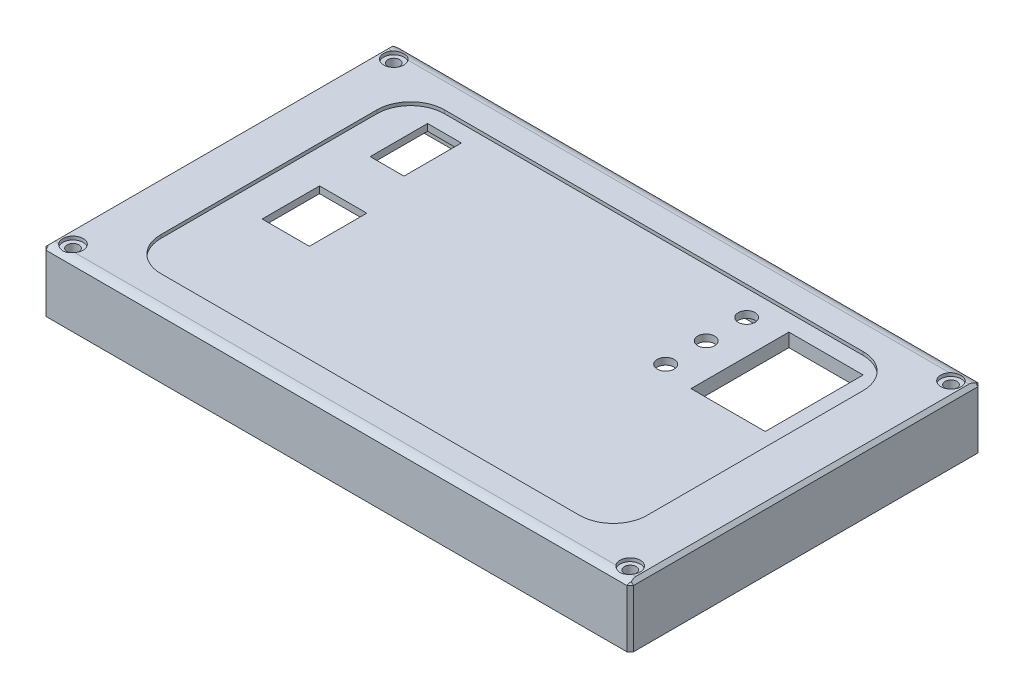
SolidWorks part; units mm, degrees
ref_plane "Front Plane" through (0, 0, 0) normal (0, 0, 1) x (1, 0, 0)
ref_plane "Top Plane" through (0, 0, 0) normal (0, 1, 0) x (1, 0, 0)
ref_plane "Right Plane" through (0, 0, 0) normal (1, 0, 0) x (0, 0, -1)
sketch "Sketch1" plane through (0, 0, 0) normal (0, 1, 0) x (1, 0, 0)
  line L1 (0, 0) -> (174, 0)
  line L2 (0, 0) -> (0, 104)
  line L3 (0, 104) -> (174, 104)
  line L4 (174, 0) -> (174, 104)
  dimension "D1" = 104
  dimension "D2" = 174
extrude "Boss-Extrude3" add sketch "Sketch1" against normal blind 18
sketch "Sketch5" plane through (0, -18, 0) normal (0, -1, 0) x (-1, 0, 0)
  line L0 (-174, 0) -> (-174, 104) construction
  line L1 (-173, 103) -> (-1, 103)
  line L2 (-173, 103) -> (-173, 1)
  line L3 (-173, 1) -> (-1, 1)
  line L4 (-1, 103) -> (-1, 1)
  line L5 (0, 0) -> (-174, 0) construction
  dimension "D1" = 172
  dimension "100mm" = 102
  dimension "D2" = 1
  dimension "D3" = 1
extrude "Cut-Extrude2" cut sketch "Sketch5" against normal blind 10
sketch "Sketch6" plane through (0, -8, 0) normal (0, -1, 0) x (1, 0, 0)
  line L0 (1, -103) -> (173, -103) construction
  line L1 (172, -102) -> (2, -102)
  line L2 (172, -102) -> (172, -2)
  line L3 (172, -2) -> (2, -2)
  line L4 (2, -102) -> (2, -2)
  line L5 (173, -103) -> (173, -1) construction
  dimension "D1" = 100
  dimension "D2" = 170
  dimension "D3" = 1
  dimension "D4" = 1
extrude "Cut-Extrude4" cut sketch "Sketch6" against normal blind 5
sketch "Sketch7" plane through (0, -3, 0) normal (0, -1, 0) x (-1, 0, 0)
  line L0 (-2, 102) -> (-172, 102) construction
  line L1 (-172, 102) -> (-172, 2) construction
  line L2 (-2, 2) -> (-2, 102) construction
  line L3 (-172, 2) -> (-2, 2) construction
  line L4 (-172, 102) -> (-172, 95.1699)
  line L5 (-172, 102) -> (-165.1699, 102)
  line L6 (-2, 102) -> (-2, 95.1699)
  line L7 (-2, 102) -> (-8.8301, 102)
  line L8 (-2, 2) -> (-2, 8.8301)
  line L9 (-2, 2) -> (-8.8301, 2)
  line L10 (-172, 2) -> (-172, 8.8301)
  line L11 (-172, 2) -> (-165.1699, 2)
  circle A0 centre (-4.5, 99.5) radius 5
  circle A1 centre (-169.5, 99.5) radius 5
  circle A2 centre (-169.5, 4.5) radius 5
  circle A3 centre (-4.5, 4.5) radius 5
  line M5 (-172, 102) -> (-172, 2)
  line M6 (-172, 2) -> (-2, 2)
  line M7 (-2, 2) -> (-2, 102)
  line M8 (-2, 102) -> (-172, 102)
  dimension "D1" = 2.5
  dimension "D2" = 2.5
  dimension "D3" = 2.5
  dimension "D4" = 2.5
  dimension "D5" = 2.5
  dimension "D6" = 2.5
  dimension "D7" = 2.5
  dimension "D8" = 2.5
extrude "Boss-Extrude4" add sketch "Sketch7" along normal blind 5 contours A2 M6 M5 | A0 M8 M7 | A3 M7 M6 | A1 M5 M8 region at (168.5382, -3, -98.5382) region at (168.5382, -3, -5.4618) region at (5.4618, -3, -98.5382) region at (5.4618, -3, -5.4618)
sketch "Sketch10" plane through (0, -8, 0) normal (0, -1, 0) x (-1, 0, 0)
  line L2 (-8.8301, 102) -> (-165.1699, 102) construction
  line L3 (-2, 8.8301) -> (-2, 95.1699) construction
  line L4 (-172, 95.1699) -> (-172, 8.8301) construction
  line L5 (-165.1699, 2) -> (-8.8301, 2) construction
  circle A0 centre (-169.5, 4.5) radius 1.75
  circle A1 centre (-4.5, 4.5) radius 1.75
  circle A2 centre (-4.5, 99.5) radius 1.75
  circle A3 centre (-169.5, 99.5) radius 1.75
  dimension "D1" = 2.5
  dimension "D2" = 2.5
  dimension "D3" = 2.5
  dimension "D4" = 2.5
  dimension "D5" = 2.5
  dimension "D6" = 2.5
extrude "Cut-Extrude5" cut sketch "Sketch10" against normal blind 8
sketch "Sketch11" plane through (0, 0, 0) normal (0, 1, 0) x (1, 0, 0)
  circle A0 centre (4.5, 99.5) radius 3
  circle A1 centre (169.5, 99.5) radius 3
  circle A2 centre (169.5, 4.5) radius 3
  circle A3 centre (4.5, 4.5) radius 3
extrude "Cut-Extrude6" cut sketch "Sketch11" against normal blind 1
sketch "Sketch12" plane through (0, 0, 0) normal (0, 1, 0) x (1, 0, 0)
  line L0 (174, 104) -> (0, 104) construction
  line L1 (15, 94) -> (159, 94)
  line L2 (15, 94) -> (15, 10)
  line L3 (15, 10) -> (159, 10)
  line L4 (159, 94) -> (159, 10)
  line L5 (0, 104) -> (0, 0) construction
  line L6 (174, 0) -> (174, 104) construction
  line L7 (0, 0) -> (174, 0) construction
  point P6 (87, 104)
  dimension "D1" = 10
  dimension "D2" = 15
  dimension "D3" = 15
  dimension "D4" = 10
extrude "Cut-Extrude7" cut sketch "Sketch12" against normal blind 1
fillet "Fillet1" radius 10 4 edges at (159, -0.5, -10) (15, -0.5, -10) (159, -0.5, -94) (15, -0.5, -94)
chamfer "Chamfer1" distance 1 angle 45 8 edges at (0, -9, -104) (0, 0, -52) (0, -9, 0) (87, 0, 0) (174, -9, 0) (174, 0, -52) (87, 0, -104) (174, -9, -104)
sketch "Sketch13" plane through (0, -1, 0) normal (0, 1, 0) x (1, 0, 0)
  line L0 (1, 104) -> (173, 104) construction
  line L1 (132, 89) -> (154, 89)
  line L2 (132, 89) -> (132, 60)
  line L3 (132, 60) -> (154, 60)
  line L4 (154, 89) -> (154, 60)
  line L5 (174, 103) -> (174, 1) construction
  dimension "D1" = 22
  dimension "D2" = 29
  dimension "D3" = 15
  dimension "D4" = 20
extrude "Cut-Extrude8" cut sketch "Sketch13" against normal blind 2
sketch "Sketch14" plane through (0, -1, 0) normal (0, 1, 0) x (1, 0, 0)
  line L0 (154, 89) -> (132, 89) construction
  line L1 (132, 89) -> (132, 60) construction
  circle A0 centre (122, 86.5) radius 2.5
  circle A1 centre (122, 74.5) radius 2.5
  circle A2 centre (122, 62.5) radius 2.5
  dimension "D1" = 0
  dimension "D2" = 0
  dimension "D3" = 12
  dimension "D4" = 12
  dimension "D5" = 2.5
  dimension "D6" = 10
extrude "Cut-Extrude9" cut sketch "Sketch14" against normal blind 2
sketch "Sketch15" plane through (0, -1, 0) normal (0, 1, 0) x (1, 0, 0)
  line L0 (8.8301, 102) -> (165.1699, 102) construction
  line L1 (162, 92) -> (98, 92)
  line L2 (162, 92) -> (162, 48)
  line L3 (162, 48) -> (98, 48)
  line L4 (98, 92) -> (98, 48)
  line L5 (172, 95.1699) -> (172, 8.8301) construction
  circle A0 centre (162, 92) radius 3
  circle A1 centre (98, 92) radius 3
  circle A2 centre (162, 48) radius 3
  circle A3 centre (98, 48) radius 3
  dimension "D1" = 44
  dimension "D2" = 10
  dimension "64" = 64
  dimension "D3" = 10
extrude "Boss-Extrude5" add sketch "Sketch15" against normal blind 5 contours A2 | A3 | A1 | A0
sketch "Sketch16" plane through (0, -6, 0) normal (0, -1, 0) x (-1, 0, 0)
  circle A0 centre (-162, 92) radius 1.75
  circle A1 centre (-98, 92) radius 1.75
  circle A2 centre (-162, 48) radius 1.75
  circle A3 centre (-98, 48) radius 1.75
extrude "Cut-Extrude10" cut sketch "Sketch16" against normal blind 3
thread "Thread1" pitch 1.27 method extrude profile "Thread Profile1" start angle 0, offset 0, length 3, pitch 1.27, diameter 3.5
ref_plane "Plane6" through (163.75, -6, -92) normal (0, 0, 1) x (1, 0, 0)
sketch "Thread Profile1" plane through (163.75, -6, -92) normal (0, 0, 1) x (1, 0, 0)
  line L0 (0, 0) -> (0, 1.27) construction
  line L11 (0, 0) -> (0, 1.1112)
  line L12 (0, 1.1112) -> (-0.6874, 0.7144)
  line L13 (-0.6874, 0.7144) -> (-0.6874, 0.3969)
  line L15 (-0.6874, 0.3969) -> (0, 0)
  line L17 (-0.6874, 0.5556) -> (0, 0.5556) construction
  point P2 (0, 0)
  dimension "Pitch" = 1.27
  dimension "Profile_Angle" = 60
  dimension "Profile_Land" = 0.3175
  dimension "Profile_Height" = 0.6874
thread "Thread2" pitch 1.27 method extrude profile "Thread Profile2" start angle 0, offset 0, length 3, pitch 1.27, diameter 3.5
ref_plane "Plane7" through (99.75, -6, -92) normal (0, 0, 1) x (1, 0, 0)
sketch "Thread Profile2" plane through (99.75, -6, -92) normal (0, 0, 1) x (1, 0, 0)
  line L0 (0, 0) -> (0, 1.27) construction
  line L11 (0, 0) -> (0, 1.1112)
  line L12 (0, 1.1112) -> (-0.6874, 0.7144)
  line L13 (-0.6874, 0.7144) -> (-0.6874, 0.3969)
  line L15 (-0.6874, 0.3969) -> (0, 0)
  line L17 (-0.6874, 0.5556) -> (0, 0.5556) construction
  point P2 (0, 0)
  dimension "Pitch" = 1.27
  dimension "Profile_Angle" = 60
  dimension "Profile_Land" = 0.3175
  dimension "Profile_Height" = 0.6874
thread "Thread3" pitch 1.27 method extrude profile "Thread Profile3" start angle 0, offset 0, length 3, pitch 1.27, diameter 3.5
ref_plane "Plane8" through (99.75, -6, -48) normal (0, 0, 1) x (1, 0, 0)
sketch "Thread Profile3" plane through (99.75, -6, -48) normal (0, 0, 1) x (1, 0, 0)
  line L0 (0, 0) -> (0, 1.27) construction
  line L11 (0, 0) -> (0, 1.1112)
  line L12 (0, 1.1112) -> (-0.6874, 0.7144)
  line L13 (-0.6874, 0.7144) -> (-0.6874, 0.3969)
  line L15 (-0.6874, 0.3969) -> (0, 0)
  line L17 (-0.6874, 0.5556) -> (0, 0.5556) construction
  point P2 (0, 0)
  dimension "Pitch" = 1.27
  dimension "Profile_Angle" = 60
  dimension "Profile_Land" = 0.3175
  dimension "Profile_Height" = 0.6874
thread "Thread4" pitch 1.27 method extrude profile "Thread Profile4" start angle 0, offset 0, length 3, pitch 1.27, diameter 3.5
ref_plane "Plane9" through (163.75, -6, -48) normal (0, 0, 1) x (1, 0, 0)
sketch "Thread Profile4" plane through (163.75, -6, -48) normal (0, 0, 1) x (1, 0, 0)
  line L0 (0, 0) -> (0, 1.27) construction
  line L11 (0, 0) -> (0, 1.1112)
  line L12 (0, 1.1112) -> (-0.6874, 0.7144)
  line L13 (-0.6874, 0.7144) -> (-0.6874, 0.3969)
  line L15 (-0.6874, 0.3969) -> (0, 0)
  line L17 (-0.6874, 0.5556) -> (0, 0.5556) construction
  point P2 (0, 0)
  dimension "Pitch" = 1.27
  dimension "Profile_Angle" = 60
  dimension "Profile_Land" = 0.3175
  dimension "Profile_Height" = 0.6874
sketch "Sketch25" plane through (0, -1, 0) normal (0, 1, 0) x (1, 0, 0)
  line L0 (154, 89) -> (132, 89) construction
  line L1 (25, 57) -> (39, 57)
  line L2 (25, 57) -> (25, 40)
  line L3 (25, 40) -> (39, 40)
  line L4 (39, 57) -> (39, 40)
  line L5 (25, 89) -> (35, 89)
  line L6 (25, 89) -> (25, 72)
  line L7 (25, 72) -> (35, 72)
  line L8 (35, 89) -> (35, 72)
  line L10 (0, 1) -> (0, 103) construction
  point P9 (25, 80.5)
  dimension "D1" = 17
  dimension "D2" = 14
  dimension "D3" = 10
  dimension "D4" = 17
  dimension "D5" = 0
  dimension "D6" = 0
  dimension "D7" = 25
  dimension "D8" = 15
extrude "Cut-Extrude11" cut sketch "Sketch25" against normal blind 2
sketch "Sketch26" plane through (0, -3, 0) normal (0, -1, 0) x (-1, 0, 0)
  line L0 (-154, 89) -> (-132, 89) construction
  line L1 (-155.5, 90.5) -> (-130.5, 90.5)
  line L2 (-155.5, 90.5) -> (-155.5, 58.5)
  line L3 (-155.5, 58.5) -> (-130.5, 58.5)
  line L4 (-130.5, 90.5) -> (-130.5, 58.5)
  line L5 (-154, 60) -> (-154, 89) construction
  line L7 (-154, 89) -> (-132, 89)
  line L8 (-154, 89) -> (-154, 60)
  line L9 (-154, 60) -> (-132, 60)
  line L10 (-132, 89) -> (-132, 60)
  dimension "D1" = 32
  dimension "D2" = 25
  dimension "D3" = 1.5
  dimension "D4" = 1.5
extrude "Boss-Extrude6" add sketch "Sketch26" along normal blind 2
fillet "Fillet3" radius 4 2 edges at (87, 0, -1) (87, 0, -103)
